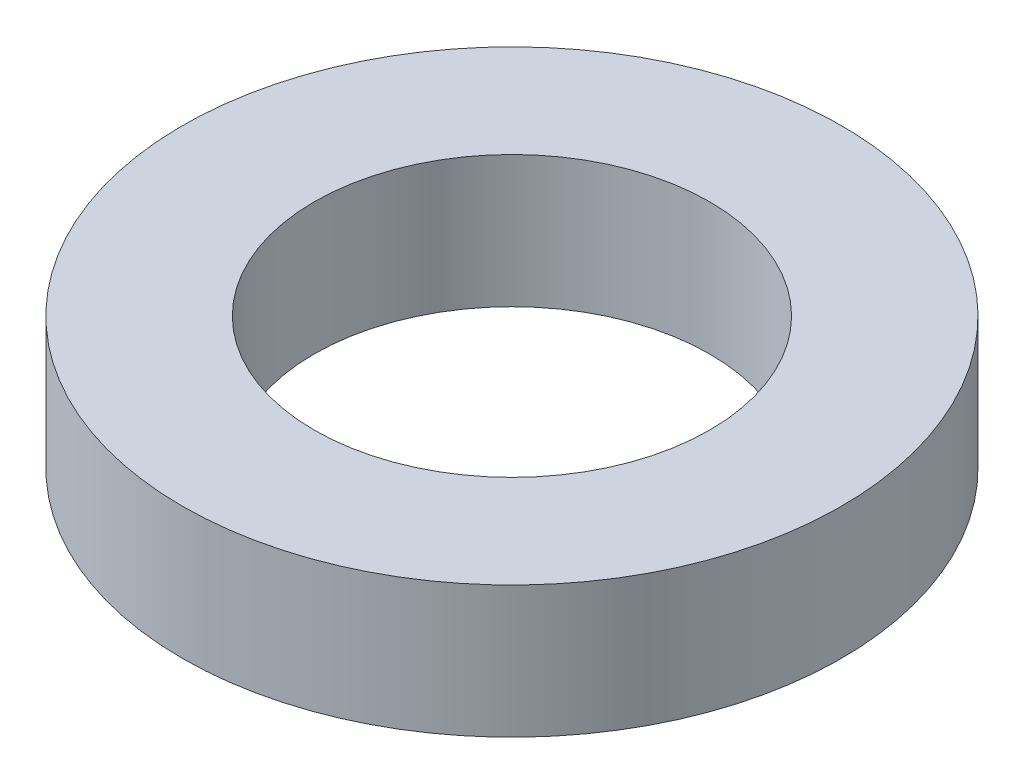
SolidWorks part; units mm, degrees
material "AISI 1020 Steel, Cold Rolled"
ref_plane "前视基准面" through (0, 0, 0) normal (0, 0, 1) x (1, 0, 0)
ref_plane "上视基准面" through (0, 0, 0) normal (0, 1, 0) x (1, 0, 0)
ref_plane "右视基准面" through (0, 0, 0) normal (1, 0, 0) x (0, 0, -1)
sketch "Sketch1" plane through (0, 0, 0) normal (0, 1, 0) x (1, 0, 0)
  circle A0 centre (0, 0) radius 1.5
  circle A1 centre (0, 0) radius 2.5
  dimension "D1" = 3
  dimension "D2" = 5
extrude "Boss-Extrude1" add sketch "Sketch1" along normal blind 1
